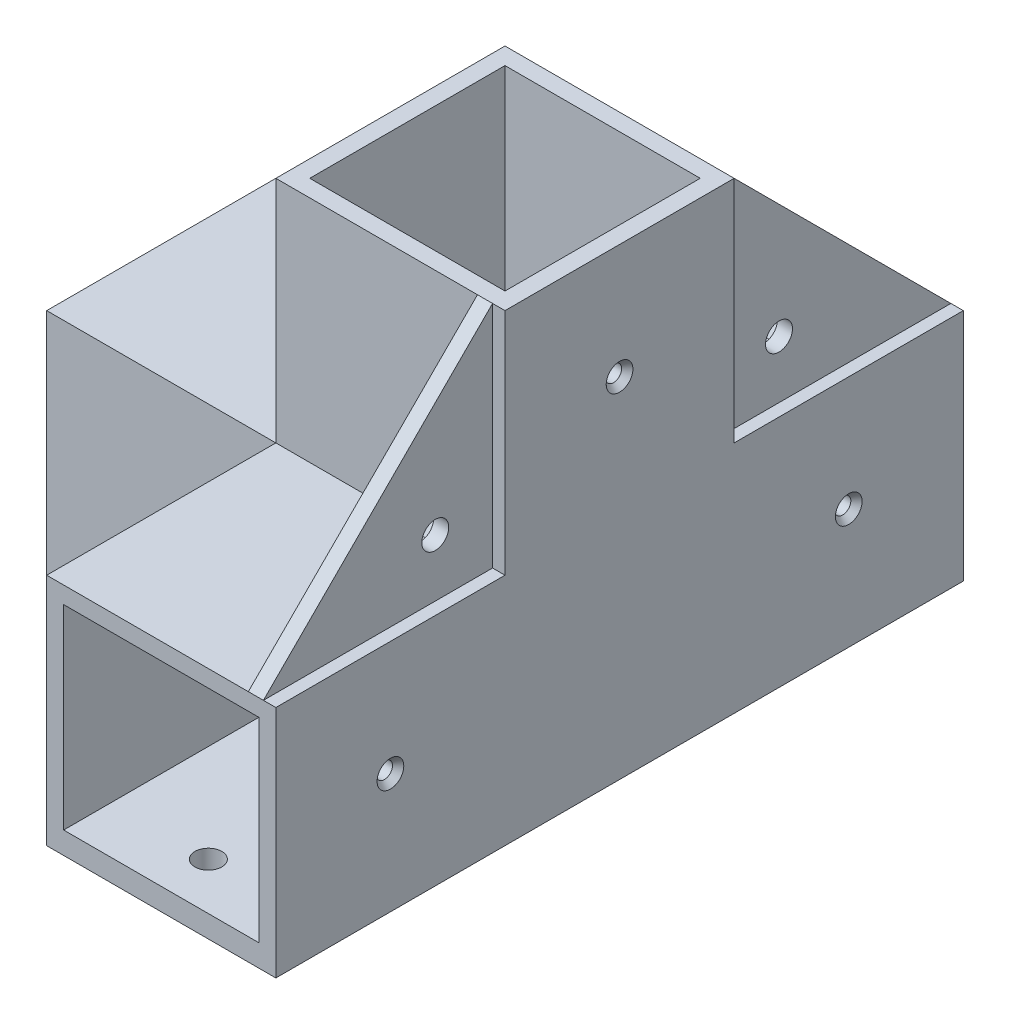
SolidWorks part; units mm, degrees
ref_plane "Plan de face" through (0, 0, 0) normal (0, 0, 1) x (1, 0, 0)
ref_plane "Plan de dessus" through (0, 0, 0) normal (0, 1, 0) x (1, 0, 0)
ref_plane "Plan de droite" through (0, 0, 0) normal (1, 0, 0) x (0, 0, -1)
sketch "Esquisse1" plane through (0, 0, 0) normal (0, 0, 1) x (1, 0, 0)
  line L0 (-30.4, 60.8) -> (30.4, -60.8) construction
  line L1 (-30.4, 60.8) -> (30.4, 60.8)
  line L2 (-30.4, 60.8) -> (-30.4, -60.8)
  line L3 (-30.4, -60.8) -> (30.4, -60.8)
  line L4 (30.4, 60.8) -> (30.4, -60.8)
  line L5 (-30.4, -60.8) -> (30.4, 60.8) construction
  point P4 (0, 0)
  dimension "D1" = 121.6
  dimension "D2" = 60.8
extrude "Boss.-Extru.1" add sketch "Esquisse1" along normal mid plane 182.4 contours L2 L3 L4 L1
sketch "Esquisse2" plane through (-30.4, 0, 0) normal (-1, 0, 0) x (0, 0, 1)
  line L1 (-91.2, 60.8) -> (-30.4, 60.8)
  line L2 (-91.2, 60.8) -> (-91.2, 0)
  line L3 (-91.2, 0) -> (-30.4, 0)
  line L4 (-30.4, 60.8) -> (-30.4, 0)
  dimension "D1" = 60.8
extrude "Enlèv. mat.-Extru.1" cut sketch "Esquisse2" against normal through all
sketch "Esquisse3" plane through (0, 0, -91.2) normal (0, 0, -1) x (-1, 0, 0)
  line L0 (-25.9, -4.5) -> (25.9, -56.3) construction
  line L1 (-25.9, -4.5) -> (25.9, -4.5)
  line L2 (-25.9, -4.5) -> (-25.9, -56.3)
  line L3 (-25.9, -56.3) -> (25.9, -56.3)
  line L4 (25.9, -4.5) -> (25.9, -56.3)
  line L5 (-25.9, -56.3) -> (25.9, -4.5) construction
  line L6 (30.4, 0) -> (30.4, -60.8) construction
  point P4 (0, -30.4)
  point P8 (30.4, -30.4)
  dimension "D1" = 51.8
extrude "Enlèv. mat.-Extru.2" cut sketch "Esquisse3" against normal blind 60.8
mirror "Symétrie2" about plane through (0, 0, 0) normal (0, 0, 1) of "Enlèv. mat.-Extru.2", "Enlèv. mat.-Extru.1"
ref_plane "Plan2" [suppressed] through (25.4, 0, 0) normal (1, 0, 0) x (0, 0, -1)
ref_plane "Plan1" through (27.1, 0, 0) normal (1, 0, 0) x (0, 0, -1)
sketch "Esquisse10" plane through (27.1, 0, 0) normal (1, 0, 0) x (0, 0, -1)
  line L0 (91.2, 0) -> (91.2, -60.8) construction
  line L2 (30.4, 60.8) -> (30.4, 0)
  line L3 (30.4, 0) -> (91.2, 0)
  line L5 (91.2, 0) -> (30.4, 0) construction
  line L6 (30.4, 60.8) -> (91.2, 0)
  line L7 (-30.4, 60.8) -> (-91.2, 0)
  line L8 (-91.2, 0) -> (-30.4, 0)
  line L9 (-30.4, 0) -> (-30.4, 60.8)
  dimension "D1" = 3.3
extrude "Boss.-Extru.3" add sketch "Esquisse10" against normal blind 4
sketch "Esquisse6" plane through (0, 60.8, 0) normal (0, 1, 0) x (1, 0, 0)
  line L0 (-25.9, 25.9) -> (25.9, -25.9) construction
  line L1 (-25.9, 25.9) -> (25.9, 25.9)
  line L2 (-25.9, 25.9) -> (-25.9, -25.9)
  line L3 (-25.9, -25.9) -> (25.9, -25.9)
  line L4 (25.9, 25.9) -> (25.9, -25.9)
  line L5 (-25.9, -25.9) -> (25.9, 25.9) construction
  point P4 (0, 0)
  dimension "D1" = 51.8
extrude "Enlèv. mat.-Extru.3" cut sketch "Esquisse6" against normal blind 60.8
sketch "Esquisse16" plane through (30.4, 0, 0) normal (1, 0, 0) x (0, 0, -1)
  line L8 (-30.4, 60.8) -> (-30.4, 0)
  line L9 (-30.4, 0) -> (-91.2, 0)
  line L10 (-91.2, 0) -> (-91.2, -60.8)
  line L11 (-91.2, -60.8) -> (91.2, -60.8)
  line L12 (91.2, -60.8) -> (91.2, 0)
  line L13 (91.2, 0) -> (30.4, 0)
  line L14 (30.4, 0) -> (30.4, 60.8)
  line L15 (30.4, 60.8) -> (-30.4, 60.8)
  line L16 (-30.4, 60.8) -> (-30.4, 0)
  line L17 (-30.4, 0) -> (-91.2, 0)
  line L18 (-91.2, 0) -> (-91.2, -60.8)
  line L19 (-91.2, -60.8) -> (91.2, -60.8)
  line L20 (91.2, -60.8) -> (91.2, 0)
  line L21 (91.2, 0) -> (30.4, 0)
  line L22 (30.4, 0) -> (30.4, 60.8)
  line L23 (30.4, 60.8) -> (-30.4, 60.8)
  dimension "D1" = 0
extrude "Boss.-Extru.4" [suppressed] add sketch "Esquisse16" along normal blind 1.35
hole_wizard "Dégagement 1/41" [suppressed] positions "Esquisse4" profile "Esquisse5" hole size "1/4" standard "Ansi Inch"
sketch "Esquisse4" [suppressed] plane through (25.4, 0, 0) normal (1, 0, 0) x (0, 0, -1)
  line L4 (60.8, 30.4) -> (30.4, 0) construction
  line L5 (91.2, 0) -> (30.4, 60.8) construction
  line L6 (-30.4, 0) -> (-60.8, 30.4) construction
  line L7 (-30.4, 60.8) -> (-91.2, 0) construction
  point P11 (45.6, 15.2)
  point P33 (45.6, 15.2)
  point P41 (-45.6, 15.2)
sketch "Esquisse5" plane through (25.4, 15.2, -45.6) normal (0, 1, 0) x (0, 0, -1)
  line L0 (0, 0) -> (0, 20)
  line L1 (0, 20) -> (3.3782, 20)
  line L2 (3.3782, 20) -> (3.3782, 0)
  line L5 (3.3782, 0) -> (0, 0)
  line L10 (0, 20) -> (-3.3782, 20) construction
  line L11 (0, -6.35) -> (0, 107.95) construction
  dimension "Diamètre du perçage" = 6.7564
  dimension "Profondeur du perçage" = 20
  dimension "Angle de pointe" = 180
hole_wizard "Fraisage pour vis à tête fraisée bombée #61" [suppressed] positions "Esquisse11" profile "Esquisse12" countersink size "#6" standard "Ansi Inch"
sketch "Esquisse11" [suppressed] plane through (31.75, 0, 0) normal (1, 0, 0) x (0, 0, -1)
  line L6 (0, 0) -> (0, -10.6338) construction
  line L12 (30.4, 0) -> (91.2, 0) construction
  point P0 (60.8, -30.4)
  point P22 (-60.8, -30.4)
  point P23 (0, 30.4)
  point P39 (60.8, -30.4)
  point P43 (60.8, 0)
  dimension "D1" = 30.4
  dimension "D2" = 30.4
sketch "Esquisse12" plane through (31.75, -30.4, -60.8) normal (0, 1, 0) x (0, 0, -1)
  line L0 (0, 0) -> (0, 20)
  line L1 (0, 20) -> (2.1526, 20)
  line L2 (2.1526, 20) -> (2.1526, 1.5998)
  line L3 (2.1526, 1.5998) -> (3.5433, 0)
  line L5 (3.5433, 0) -> (0, 0)
  line L6 (-2.1526, 1.5998) -> (-3.5433, 0) construction
  line L10 (0, 20) -> (-2.1527, 20) construction
  line L11 (0, -6.35) -> (0, 107.95) construction
  dimension "Diamètre du perçage" = 4.3053
  dimension "Profondeur du perçage" = 20
  dimension "Diamètre du fraisage entrant" = 7.0866
  dimension "Angle du fraisage entrant" = 82
  dimension "Angle de pointe" = 180
hole_wizard "Dégagement 1/43" positions "Esquisse17" profile "Esquisse19" hole size "1/4" standard "Ansi Inch" end condition through all
sketch "Esquisse17" plane through (27.1, 0, 0) normal (1, 0, 0) x (0, 0, -1)
  line L0 (-60.8, 30.4) -> (-30.4, 0) construction
  line L1 (-30.4, 60.8) -> (-91.2, 0) construction
  line L3 (60.8, 30.4) -> (30.4, 0) construction
  line L4 (91.2, 0) -> (30.4, 60.8) construction
  point P15 (-45.6, 15.2)
  point P17 (45.6, 15.2)
sketch "Esquisse19" plane through (27.1, 15.2, -45.6) normal (0, 1, 0) x (0, 0, -1)
  line L0 (0, 0) -> (0, 57.5)
  line L1 (0, 57.5) -> (3.5712, 57.5)
  line L2 (3.5712, 57.5) -> (3.5712, 0)
  line L5 (3.5712, 0) -> (0, 0)
  line L11 (0, -6.35) -> (0, 107.95) construction
  dimension "Diamètre du perçage jusqu'au prochain" = 7.1425
  dimension "Profondeur du perçage jusqu'au prochain" = 57.5
hole_wizard "Fraisage pour vis à tête fraisée bombée #62" positions "Esquisse22" profile "Esquisse21" countersink size "#6" standard "Ansi Inch" end condition up to next
sketch "Esquisse22" plane through (30.4, 0, 0) normal (1, 0, 0) x (0, 0, -1)
  line L0 (-60.8, 0) -> (-60.8, -30.4) construction
  line L1 (-91.2, 0) -> (-30.4, 0) construction
  line L10 (30.4, 0) -> (91.2, 0) construction
  line L11 (60.8, -30.4) -> (-60.8, -30.4) construction
  point P23 (0, 30.4)
  point P25 (60.8, -30.4)
  point P29 (60.8, 0)
  point P36 (-60.8, -30.4)
  dimension "D1" = 30.4
  dimension "D2" = 30.4
sketch "Esquisse21" plane through (30.4, -30.4, 60.8) normal (0, 1, 0) x (0, 0, -1)
  line L0 (0, 0) -> (0, 4.5)
  line L1 (0, 4.5) -> (2.1526, 4.5)
  line L2 (2.1526, 4.5) -> (2.1526, 1.5998)
  line L3 (2.1526, 1.5998) -> (3.5433, 0)
  line L5 (3.5433, 0) -> (0, 0)
  line L6 (-2.1526, 1.5998) -> (-3.5433, 0) construction
  line L11 (0, -6.35) -> (0, 107.95) construction
  dimension "Diamètre du perçage jusqu'au prochain" = 4.3053
  dimension "Profondeur du perçage jusqu'au prochain" = 4.5
  dimension "Diamètre du fraisage entrant" = 7.0866
  dimension "Angle du fraisage entrant" = 82
hole_wizard "Dégagement 1/42" positions "Esquisse14" profile "Esquisse15" hole size "1/4" standard "Ansi Inch"
sketch "Esquisse14" plane through (0, -60.8, 0) normal (0, -1, 0) x (-1, 0, 0)
  point P13 (0, 78.7)
  point P15 (0, -78.7)
  dimension "D2" = 78.7
  dimension "D3" = 78.7
sketch "Esquisse15" plane through (0, -60.8, -78.7) normal (1, 0, 0) x (0, 0, -1)
  line L0 (0, 0) -> (0, 20)
  line L1 (0, 20) -> (3.5712, 20)
  line L2 (3.5712, 20) -> (3.5712, 0)
  line L5 (3.5712, 0) -> (0, 0)
  line L10 (0, 20) -> (-3.5712, 20) construction
  line L11 (0, -6.35) -> (0, 107.95) construction
  dimension "Diamètre du perçage" = 7.1425
  dimension "Profondeur du perçage" = 20
  dimension "Angle de pointe" = 180
sketch "Esquisse23" plane through (23.1, 0, 0) normal (-1, 0, 0) x (0, 0, 1)
  line L0 (-41.1977, 22.825) -> (-50.0023, 22.825)
  line L1 (-40.2595, 15.2) -> (-42.9298, 19.825)
  line L2 (-42.9298, 19.825) -> (-48.2702, 19.825)
  line L3 (-48.2702, 19.825) -> (-50.9405, 15.2)
  line L4 (-50.9405, 15.2) -> (-48.2702, 10.575)
  line L5 (-48.2702, 10.575) -> (-42.9298, 10.575)
  line L6 (-42.9298, 10.575) -> (-40.2595, 15.2)
  line L7 (50.9405, 15.2) -> (48.2702, 19.825)
  line L8 (48.2702, 19.825) -> (42.9298, 19.825)
  line L9 (42.9298, 19.825) -> (40.2595, 15.2)
  line L10 (40.2595, 15.2) -> (42.9298, 10.575)
  line L11 (42.9298, 10.575) -> (48.2702, 10.575)
  line L12 (48.2702, 10.575) -> (50.9405, 15.2)
  line L13 (-50.0023, 22.825) -> (-54.4046, 15.2)
  line L14 (-54.4046, 15.2) -> (-50.0023, 7.575)
  line L15 (-50.0023, 7.575) -> (-41.1977, 7.575)
  line L16 (-41.1977, 7.575) -> (-36.7954, 15.2)
  line L17 (-36.7954, 15.2) -> (-41.1977, 22.825)
  line L18 (54.4046, 15.2) -> (50.0023, 22.825)
  line L19 (50.0023, 22.825) -> (41.1977, 22.825)
  line L20 (41.1977, 22.825) -> (36.7954, 15.2)
  line L21 (36.7954, 15.2) -> (41.1977, 7.575)
  line L22 (41.1977, 7.575) -> (50.0023, 7.575)
  line L23 (50.0023, 7.575) -> (54.4046, 15.2)
  circle A0 centre (-45.6, 15.2) radius 4.625 construction
  circle A1 centre (45.6, 15.2) radius 4.625 construction
  dimension "D1" = 9.25
  dimension "D2" = 3
  dimension "D3" = 3
extrude "Boss.-Extru.5" add sketch "Esquisse23" along normal blind 4
chamfer "Chanfrein1" distance 4 angle 45 12 edges at (23.1, 19.0125, 38.9966) (23.1, 11.3875, 38.9966) (23.1, 7.575, 45.6) (23.1, 11.3875, 52.2034) (23.1, 19.0125, 52.2034) (23.1, 22.825, 45.6) (23.1, 11.3875, -38.9966) (23.1, 19.0125, -38.9966) (23.1, 7.575, -45.6) (23.1, 11.3875, -52.2034) (23.1, 22.825, -45.6) (23.1, 19.0125, -52.2034)
sketch "Esquisse25" [suppressed] plane through (21.4, 0, 0) normal (-1, 0, 0) x (0, 0, 1)
  line L0 (-36.7954, 15.2) -> (-41.1977, 22.825)
  line L1 (-40.2595, 15.2) -> (-42.9298, 19.825)
  line L2 (-42.9298, 19.825) -> (-48.2702, 19.825)
  line L3 (-48.2702, 19.825) -> (-50.9405, 15.2)
  line L4 (-50.9405, 15.2) -> (-48.2702, 10.575)
  line L5 (-48.2702, 10.575) -> (-42.9298, 10.575)
  line L6 (-42.9298, 10.575) -> (-40.2595, 15.2)
  line L7 (50.9405, 15.2) -> (48.2702, 19.825)
  line L8 (48.2702, 19.825) -> (42.9298, 19.825)
  line L9 (42.9298, 19.825) -> (40.2595, 15.2)
  line L10 (40.2595, 15.2) -> (42.9298, 10.575)
  line L11 (42.9298, 10.575) -> (48.2702, 10.575)
  line L12 (48.2702, 10.575) -> (50.9405, 15.2)
  line L13 (-41.1977, 22.825) -> (-50.0023, 22.825)
  line L14 (-50.0023, 22.825) -> (-54.4046, 15.2)
  line L15 (-54.4046, 15.2) -> (-50.0023, 7.575)
  line L16 (-50.0023, 7.575) -> (-41.1977, 7.575)
  line L17 (-41.1977, 7.575) -> (-36.7954, 15.2)
  line L18 (50.0023, 22.825) -> (41.1977, 22.825)
  line L19 (41.1977, 22.825) -> (36.7954, 15.2)
  line L20 (36.7954, 15.2) -> (41.1977, 7.575)
  line L21 (41.1977, 7.575) -> (50.0023, 7.575)
  line L22 (50.0023, 7.575) -> (54.4046, 15.2)
  line L23 (54.4046, 15.2) -> (50.0023, 22.825)
  circle A0 centre (-45.6, 15.2) radius 4.625 construction
  circle A1 centre (45.6, 15.2) radius 4.625 construction
  dimension "D1" = 9.25
  dimension "D2" = 3
extrude "Boss.-Extru.6" [suppressed] add sketch "Esquisse25" along normal blind 4
chamfer "Chanfrein2" [suppressed] distance 4 angle 45
sketch "Esquisse26" plane through (-30.4, 0, 0) normal (-1, 0, 0) x (0, 0, 1)
  line L0 (91.2, -60.8) -> (-91.2, -60.8) construction
  line L1 (30.4, 0) -> (-30.4, 0)
  line L2 (30.4, 0) -> (30.4, -60.8)
  line L3 (30.4, -60.8) -> (-30.4, -60.8)
  line L4 (-30.4, 0) -> (-30.4, -60.8)
  line L5 (30.4, 0) -> (-30.4, -60.8) construction
  line L6 (30.4, -60.8) -> (-30.4, 0) construction
  line L8 (25.9, -56.3) -> (-25.9, -56.3)
  line L9 (25.9, -56.3) -> (25.9, -4.5)
  line L10 (25.9, -4.5) -> (-25.9, -4.5)
  line L11 (-25.9, -56.3) -> (-25.9, -4.5)
  line L12 (25.9, -56.3) -> (-25.9, -4.5) construction
  line L13 (25.9, -4.5) -> (-25.9, -56.3) construction
  point P4 (0, -30.4)
  point P10 (0, -30.4)
  dimension "D1" = 51.8
extrude "Boss.-Extru.8" add sketch "Esquisse26" along normal blind 60.8
sketch "Esquisse27" plane through (0, -60.8, 0) normal (0, -1, 0) x (1, 0, 0)
  line L8 (-30.4, -91.2) -> (30.4, -91.2)
  line L9 (30.4, -91.2) -> (30.4, 91.2)
  line L10 (30.4, 91.2) -> (-30.4, 91.2)
  line L11 (-30.4, 91.2) -> (-30.4, 30.4)
  line L12 (-30.4, 30.4) -> (-91.2, 30.4)
  line L13 (-91.2, 30.4) -> (-91.2, -30.4)
  line L14 (-91.2, -30.4) -> (-30.4, -30.4)
  line L15 (-30.4, -30.4) -> (-30.4, -91.2)
  line L16 (-30.4, -91.2) -> (30.4, -91.2)
  line L18 (30.4, 91.2) -> (-30.4, 91.2)
  line L19 (-30.4, 91.2) -> (-30.4, 30.4)
  line L20 (-30.4, 30.4) -> (-91.2, 30.4)
  line L21 (-91.2, 30.4) -> (-91.2, -30.4)
  line L22 (-91.2, -30.4) -> (-30.4, -30.4)
  line L23 (-30.4, -30.4) -> (-30.4, -91.2)
  line L26 (30.4, -91.2) -> (30.4, 91.2)
  circle A1 centre (0, 78.7) radius 3.5712
  circle A2 centre (0, 78.7) radius 3.5712
  circle A3 centre (0, -78.7) radius 3.5712
  circle A4 centre (0, -78.7) radius 3.5712
  dimension "D1" = 0
  dimension "D2" = 0
  dimension "D3" = 0
extrude "Boss.-Extru.9" add sketch "Esquisse27" along normal blind 1.35
